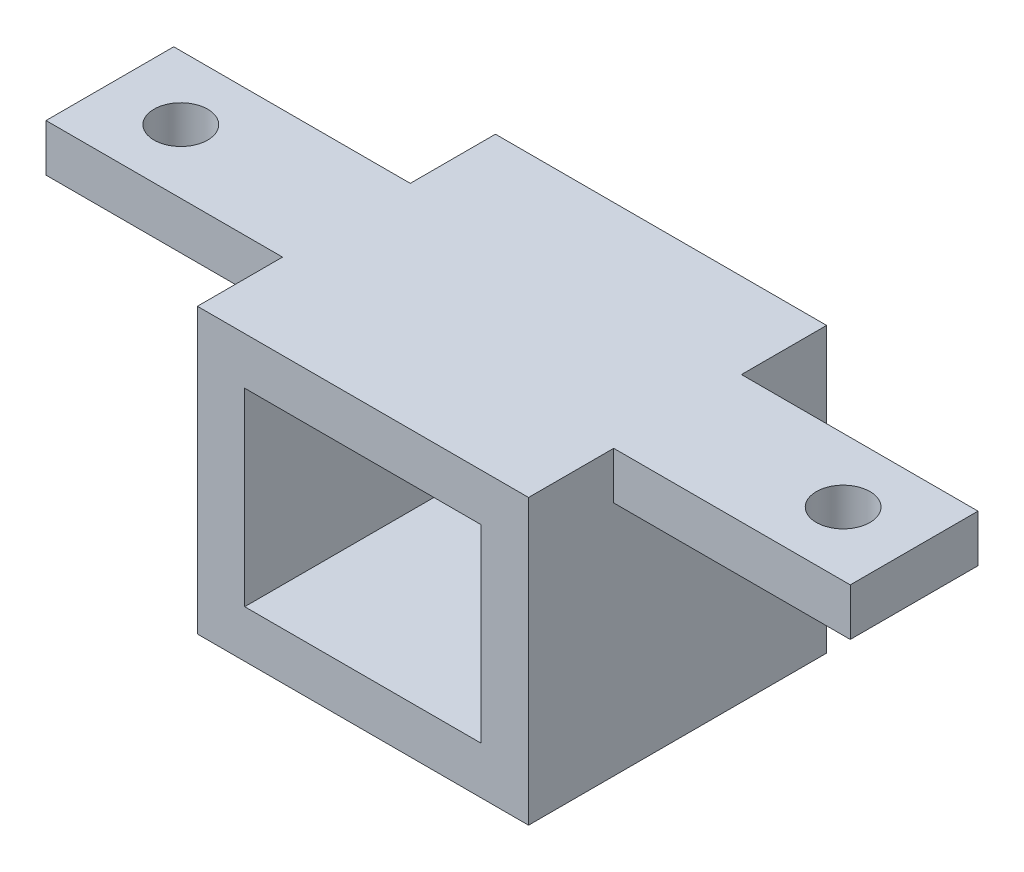
SolidWorks part; units mm, degrees
ref_plane "Front Plane" through (0, 0, 0) normal (0, 0, 1) x (1, 0, 0)
ref_plane "Top Plane" through (0, 0, 0) normal (0, 1, 0) x (1, 0, 0)
ref_plane "Right Plane" through (0, 0, 0) normal (1, 0, 0) x (0, 0, -1)
sketch "Sketch1" plane through (0, 0, 0) normal (0, 1, 0) x (1, 0, 0)
  line L1 (8.89, -8.001) -> (-8.89, -8.001)
  line L2 (8.89, -8.001) -> (8.89, 8.001)
  line L3 (8.89, 8.001) -> (-8.89, 8.001)
  line L4 (-8.89, -8.001) -> (-8.89, 8.001)
  line L5 (0, 8.001) -> (0, -8.001) construction
  line L6 (8.89, 0) -> (-8.89, 0) construction
  line L7 (-8.89, 3.429) -> (-21.59, 3.429)
  line L8 (-8.89, 3.429) -> (-8.89, -3.429)
  line L9 (-8.89, -3.429) -> (-21.59, -3.429)
  line L10 (-21.59, 3.429) -> (-21.59, -3.429)
  line L11 (8.89, 3.429) -> (21.59, 3.429)
  line L12 (8.89, 3.429) -> (8.89, -3.429)
  line L13 (8.89, -3.429) -> (21.59, -3.429)
  line L14 (21.59, 3.429) -> (21.59, -3.429)
  point P0 (0, 0)
  point P12 (0, 0)
  dimension "D1" = 12.7
  dimension "D2" = 12.7
  dimension "D3" = 17.78
  dimension "D4" = 4.572
  dimension "D5" = 16.002
  dimension "D6" = 4.572
  dimension "D7" = 4.572
  dimension "D8" = 4.572
extrude "Boss-Extrude1" add sketch "Sketch1" along normal blind 2.54 contours L4 L1 L2 L3 | L7 L10 L9 L4 | L14 L11 L2 L13 region at (0, 0, 0) region at (15.24, 0, 0) region at (-15.24, 0, 0)
sketch "Sketch2" plane through (0, 0, 0) normal (0, -1, 0) x (1, 0, 0)
  line L0 (21.59, -3.429) -> (21.59, 3.429) construction
  line L1 (-21.59, -3.429) -> (-21.59, 3.429) construction
  circle A0 centre (-17.78, 0) radius 1.44
  circle A1 centre (17.78, 0) radius 1.44
  dimension "D1" = 3.81
  dimension "D2" = 3.81
extrude "Cut-Extrude1" cut sketch "Sketch2" against normal through all contours A1 | A0
sketch "Sketch3" plane through (0, 0, 0) normal (0, -1, 0) x (-1, 0, 0)
  line L0 (-8.89, 8.001) -> (8.89, 8.001) construction
  line L1 (8.89, -8.001) -> (6.35, -8.001)
  line L2 (8.89, -8.001) -> (8.89, 8.001)
  line L3 (8.89, 8.001) -> (6.35, 8.001)
  line L4 (6.35, -8.001) -> (6.35, 8.001)
  line L6 (-8.89, -8.001) -> (-6.35, -8.001)
  line L7 (-8.89, -8.001) -> (-8.89, 8.001)
  line L8 (-8.89, 8.001) -> (-6.35, 8.001)
  line L9 (-6.35, -8.001) -> (-6.35, 8.001)
  line L10 (6.35, 8.001) -> (-6.35, 8.001)
  line L11 (6.35, 8.001) -> (6.35, 5.461)
  line L12 (6.35, 5.461) -> (-6.35, 5.461)
  line L13 (-6.35, 8.001) -> (-6.35, 5.461)
  line M9 (8.89, -8.001) -> (8.89, -3.429)
  line M13 (8.89, 3.429) -> (8.89, 8.001)
  line M14 (8.89, 8.001) -> (-8.89, 8.001)
  line M15 (-8.89, 8.001) -> (-8.89, 3.429)
  line M19 (-8.89, -3.429) -> (-8.89, -8.001)
  line M20 (-8.89, -8.001) -> (8.89, -8.001)
  dimension "D1" = 2.54
  dimension "D2" = 2.54
  dimension "D3" = 2.54
extrude "Boss-Extrude2" add sketch "Sketch3" along normal blind 10.16 contours L4 L2 M20 M9 M13 M14 | L12 L4 L9 M14 | L9 L7 M20 M14 M15 M19 region at (-7.62, 0, 0) region at (0, 0, -6.731) region at (7.62, 0, 0)
sketch "Sketch4" plane through (0, -10.16, 0) normal (0, -1, 0) x (-1, 0, 0)
  line L1 (8.89, -8.001) -> (-8.89, -8.001)
  line L2 (8.89, -8.001) -> (8.89, 8.001)
  line L3 (8.89, 8.001) -> (-8.89, 8.001)
  line L4 (-8.89, -8.001) -> (-8.89, 8.001)
extrude "Boss-Extrude3" add sketch "Sketch4" along normal blind 2.54
sketch "Sketch5" plane through (0, 0, -8.001) normal (0, 0, -1) x (-1, 0, 0)
  line L0 (8.89, -12.7) -> (-8.89, -12.7) construction
  line L2 (-8.89, 2.54) -> (-8.89, -12.7) construction
  line L3 (8.89, 2.54) -> (8.89, -12.7) construction
  circle A0 centre (0, -5.08) radius 1.778
  circle A1 centre (5.334, -5.08) radius 0.508
  circle A2 centre (-5.334, -5.08) radius 0.508
  dimension "D1" = 7.62
  dimension "D2" = 7.62
  dimension "D3" = 7.62
  dimension "D4" = 3.556
  dimension "D5" = 3.556
extrude "Cut-Extrude2" cut sketch "Sketch5" against normal through all contours A2 | A0 | A1
